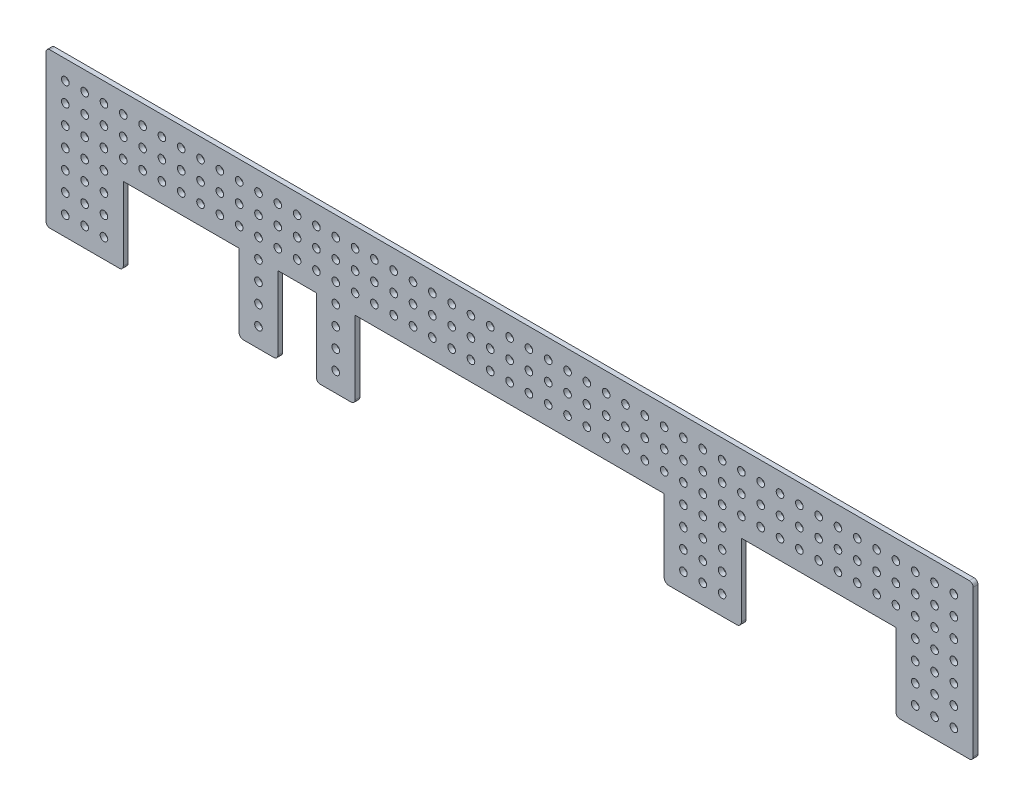
SolidWorks part; units mm, degrees
ref_plane "Front Plane" through (0, 0, 0) normal (0, 0, 1) x (1, 0, 0)
ref_plane "Top Plane" through (0, 0, 0) normal (0, 1, 0) x (1, 0, 0)
ref_plane "Right Plane" through (0, 0, 0) normal (1, 0, 0) x (0, 0, -1)
sketch "Sketch2" plane through (0, 0, 0) normal (0, 0, 1) x (1, 0, 0)
  line L1 (-478.1332, -46.4778) -> (126.3868, -46.4778)
  line L2 (-480.6732, -49.0178) -> (-480.6732, -97.2778)
  line L3 (-480.6732, -97.2778) -> (128.9268, -97.2778)
  line L4 (128.9268, -49.0178) -> (128.9268, -97.2778)
  line L5 (-480.6732, -97.2778) -> (-429.8732, -97.2778)
  line L6 (-480.6732, -97.2778) -> (-480.6732, -145.5378)
  line L7 (-478.1332, -148.0778) -> (-432.4132, -148.0778)
  line L8 (-429.8732, -97.2778) -> (-429.8732, -145.5378)
  line L9 (78.1268, -97.2778) -> (128.9268, -97.2778)
  line L10 (78.1268, -97.2778) -> (78.1268, -145.5378)
  line L11 (80.6668, -148.0778) -> (126.3868, -148.0778)
  line L12 (128.9268, -97.2778) -> (128.9268, -145.5378)
  arc A0 (78.1268, -145.5378) -> (80.6668, -148.0778) centre (80.6668, -145.5378) ccw
  arc A1 (126.3868, -148.0778) -> (128.9268, -145.5378) centre (126.3868, -145.5378) ccw
  arc A2 (126.3868, -46.4778) -> (128.9268, -49.0178) centre (126.3868, -49.0178) cw
  arc A3 (-432.4132, -148.0778) -> (-429.8732, -145.5378) centre (-432.4132, -145.5378) ccw
  arc A4 (-480.6732, -145.5378) -> (-478.1332, -148.0778) centre (-478.1332, -145.5378) ccw
  arc A5 (-478.1332, -46.4778) -> (-480.6732, -49.0178) centre (-478.1332, -49.0178) ccw
  point P16 (78.1268, -148.0778)
  point P19 (128.9268, -148.0778)
  point P22 (128.9268, -46.4778)
  point P25 (-429.8732, -148.0778)
  point P28 (-480.6732, -148.0778)
  dimension "D7" = 2.54
  dimension "D1" = 50.8
  dimension "D2" = 609.6
  dimension "D3" = 50.8
  dimension "D4" = 50.8
  dimension "3" = 50.8
  dimension "D6" = 50.8
extrude "Boss-Extrude1" add sketch "Sketch2" along normal blind 3.175 contours L4 L1 L2 L3 | L8 L3 L6 L7 | L12 L3 L10 L11 region at (-175.8732, -71.88, 0) region at (-455.2732, -122.6511, 0) region at (103.5268, -122.6511, 0)
sketch "Sketch3" plane through (0, 0, 3.175) normal (0, 0, 1) x (1, 0, 0)
  line L0 (-478.1332, -46.4778) -> (126.3868, -46.4778) construction
  line L1 (-480.6732, -49.0178) -> (-480.6732, -145.5378) construction
  line L2 (-478.1332, -148.0778) -> (-432.4132, -148.0778) construction
  line L3 (80.6668, -148.0778) -> (126.3868, -148.0778) construction
  line L4 (78.1268, -97.2778) -> (78.1268, -145.5378) construction
  circle A0 centre (-467.9732, -59.1778) radius 2.505
  circle A1 centre (-455.2732, -59.1778) radius 2.505
  circle A2 centre (-442.5732, -59.1778) radius 2.505
  circle A3 centre (-429.8732, -59.1778) radius 2.505
  circle A4 centre (-417.1732, -59.1778) radius 2.505
  circle A5 centre (-404.4732, -59.1778) radius 2.505
  circle A6 centre (-391.7732, -59.1778) radius 2.505
  circle A7 centre (-379.0732, -59.1778) radius 2.505
  circle A8 centre (-366.3732, -59.1778) radius 2.505
  circle A9 centre (-353.6732, -59.1778) radius 2.505
  circle A10 centre (-340.9732, -59.1778) radius 2.505
  circle A11 centre (-328.2732, -59.1778) radius 2.505
  circle A12 centre (-315.5732, -59.1778) radius 2.505
  circle A13 centre (-302.8732, -59.1778) radius 2.505
  circle A14 centre (-290.1732, -59.1778) radius 2.505
  circle A15 centre (-277.4732, -59.1778) radius 2.505
  circle A16 centre (-264.7732, -59.1778) radius 2.505
  circle A17 centre (-252.0732, -59.1778) radius 2.505
  circle A18 centre (-239.3732, -59.1778) radius 2.505
  circle A19 centre (-226.6732, -59.1778) radius 2.505
  circle A20 centre (-213.9732, -59.1778) radius 2.505
  circle A21 centre (-201.2732, -59.1778) radius 2.505
  circle A22 centre (-188.5732, -59.1778) radius 2.505
  circle A23 centre (-175.8732, -59.1778) radius 2.505
  circle A24 centre (-163.1732, -59.1778) radius 2.505
  circle A25 centre (-150.4732, -59.1778) radius 2.505
  circle A26 centre (-137.7732, -59.1778) radius 2.505
  circle A27 centre (-125.0732, -59.1778) radius 2.505
  circle A28 centre (-112.3732, -59.1778) radius 2.505
  circle A29 centre (-99.6732, -59.1778) radius 2.505
  circle A30 centre (-86.9732, -59.1778) radius 2.505
  circle A31 centre (-74.2732, -59.1778) radius 2.505
  circle A32 centre (-61.5732, -59.1778) radius 2.505
  circle A33 centre (-48.8732, -59.1778) radius 2.505
  circle A34 centre (-36.1732, -59.1778) radius 2.505
  circle A35 centre (-23.4732, -59.1778) radius 2.505
  circle A36 centre (-10.7732, -59.1778) radius 2.505
  circle A37 centre (1.9268, -59.1778) radius 2.505
  circle A38 centre (14.6268, -59.1778) radius 2.505
  circle A39 centre (27.3268, -59.1778) radius 2.505
  circle A40 centre (40.0268, -59.1778) radius 2.505
  circle A41 centre (52.7268, -59.1778) radius 2.505
  circle A42 centre (65.4268, -59.1778) radius 2.505
  circle A43 centre (78.1268, -59.1778) radius 2.505
  circle A44 centre (90.8268, -59.1778) radius 2.505
  circle A45 centre (103.5268, -59.1778) radius 2.505
  circle A46 centre (116.2268, -59.1778) radius 2.505
  circle A47 centre (-455.2732, -71.8778) radius 2.505
  circle A48 centre (-442.5732, -71.8778) radius 2.505
  circle A49 centre (-429.8732, -71.8778) radius 2.505
  circle A50 centre (-417.1732, -71.8778) radius 2.505
  circle A51 centre (-404.4732, -71.8778) radius 2.505
  circle A52 centre (-391.7732, -71.8778) radius 2.505
  circle A53 centre (-379.0732, -71.8778) radius 2.505
  circle A54 centre (-366.3732, -71.8778) radius 2.505
  circle A55 centre (-353.6732, -71.8778) radius 2.505
  circle A56 centre (-340.9732, -71.8778) radius 2.505
  circle A57 centre (-328.2732, -71.8778) radius 2.505
  circle A58 centre (-315.5732, -71.8778) radius 2.505
  circle A59 centre (-302.8732, -71.8778) radius 2.505
  circle A60 centre (-290.1732, -71.8778) radius 2.505
  circle A61 centre (-277.4732, -71.8778) radius 2.505
  circle A62 centre (-264.7732, -71.8778) radius 2.505
  circle A63 centre (-252.0732, -71.8778) radius 2.505
  circle A64 centre (-239.3732, -71.8778) radius 2.505
  circle A65 centre (-226.6732, -71.8778) radius 2.505
  circle A66 centre (-213.9732, -71.8778) radius 2.505
  circle A67 centre (-201.2732, -71.8778) radius 2.505
  circle A68 centre (-188.5732, -71.8778) radius 2.505
  circle A69 centre (-175.8732, -71.8778) radius 2.505
  circle A70 centre (-163.1732, -71.8778) radius 2.505
  circle A71 centre (-150.4732, -71.8778) radius 2.505
  circle A72 centre (-137.7732, -71.8778) radius 2.505
  circle A73 centre (-125.0732, -71.8778) radius 2.505
  circle A74 centre (-112.3732, -71.8778) radius 2.505
  circle A75 centre (-99.6732, -71.8778) radius 2.505
  circle A76 centre (-86.9732, -71.8778) radius 2.505
  circle A77 centre (-74.2732, -71.8778) radius 2.505
  circle A78 centre (-61.5732, -71.8778) radius 2.505
  circle A79 centre (-48.8732, -71.8778) radius 2.505
  circle A80 centre (-36.1732, -71.8778) radius 2.505
  circle A81 centre (-23.4732, -71.8778) radius 2.505
  circle A82 centre (-10.7732, -71.8778) radius 2.505
  circle A83 centre (1.9268, -71.8778) radius 2.505
  circle A84 centre (14.6268, -71.8778) radius 2.505
  circle A85 centre (27.3268, -71.8778) radius 2.505
  circle A86 centre (40.0268, -71.8778) radius 2.505
  circle A87 centre (52.7268, -71.8778) radius 2.505
  circle A88 centre (65.4268, -71.8778) radius 2.505
  circle A89 centre (78.1268, -71.8778) radius 2.505
  circle A90 centre (90.8268, -71.8778) radius 2.505
  circle A91 centre (103.5268, -71.8778) radius 2.505
  circle A92 centre (116.2268, -71.8778) radius 2.505
  circle A93 centre (-455.2732, -84.5778) radius 2.505
  circle A94 centre (-442.5732, -84.5778) radius 2.505
  circle A95 centre (-429.8732, -84.5778) radius 2.505
  circle A96 centre (-417.1732, -84.5778) radius 2.505
  circle A97 centre (-404.4732, -84.5778) radius 2.505
  circle A98 centre (-391.7732, -84.5778) radius 2.505
  circle A99 centre (-379.0732, -84.5778) radius 2.505
  circle A100 centre (-366.3732, -84.5778) radius 2.505
  circle A101 centre (-353.6732, -84.5778) radius 2.505
  circle A102 centre (-340.9732, -84.5778) radius 2.505
  circle A103 centre (-328.2732, -84.5778) radius 2.505
  circle A104 centre (-315.5732, -84.5778) radius 2.505
  circle A105 centre (-302.8732, -84.5778) radius 2.505
  circle A106 centre (-290.1732, -84.5778) radius 2.505
  circle A107 centre (-277.4732, -84.5778) radius 2.505
  circle A108 centre (-264.7732, -84.5778) radius 2.505
  circle A109 centre (-252.0732, -84.5778) radius 2.505
  circle A110 centre (-239.3732, -84.5778) radius 2.505
  circle A111 centre (-226.6732, -84.5778) radius 2.505
  circle A112 centre (-213.9732, -84.5778) radius 2.505
  circle A113 centre (-201.2732, -84.5778) radius 2.505
  circle A114 centre (-188.5732, -84.5778) radius 2.505
  circle A115 centre (-175.8732, -84.5778) radius 2.505
  circle A116 centre (-163.1732, -84.5778) radius 2.505
  circle A117 centre (-150.4732, -84.5778) radius 2.505
  circle A118 centre (-137.7732, -84.5778) radius 2.505
  circle A119 centre (-125.0732, -84.5778) radius 2.505
  circle A120 centre (-112.3732, -84.5778) radius 2.505
  circle A121 centre (-99.6732, -84.5778) radius 2.505
  circle A122 centre (-86.9732, -84.5778) radius 2.505
  circle A123 centre (-74.2732, -84.5778) radius 2.505
  circle A124 centre (-61.5732, -84.5778) radius 2.505
  circle A125 centre (-48.8732, -84.5778) radius 2.505
  circle A126 centre (-36.1732, -84.5778) radius 2.505
  circle A127 centre (-23.4732, -84.5778) radius 2.505
  circle A128 centre (-10.7732, -84.5778) radius 2.505
  circle A129 centre (1.9268, -84.5778) radius 2.505
  circle A130 centre (14.6268, -84.5778) radius 2.505
  circle A131 centre (27.3268, -84.5778) radius 2.505
  circle A132 centre (40.0268, -84.5778) radius 2.505
  circle A133 centre (52.7268, -84.5778) radius 2.505
  circle A134 centre (65.4268, -84.5778) radius 2.505
  circle A135 centre (78.1268, -84.5778) radius 2.505
  circle A136 centre (90.8268, -84.5778) radius 2.505
  circle A137 centre (103.5268, -84.5778) radius 2.505
  circle A138 centre (116.2268, -84.5778) radius 2.505
  circle A139 centre (-467.9732, -71.8778) radius 2.505
  circle A140 centre (-467.9732, -84.5778) radius 2.505
  circle A141 centre (-467.9732, -135.3778) radius 2.505
  circle A142 centre (-455.2732, -135.3778) radius 2.505
  circle A143 centre (-442.5732, -135.3778) radius 2.505
  circle A144 centre (-455.2732, -122.6778) radius 2.505
  circle A145 centre (-442.5732, -122.6778) radius 2.505
  circle A146 centre (-455.2732, -109.9778) radius 2.505
  circle A147 centre (-442.5732, -109.9778) radius 2.505
  circle A148 centre (-455.2732, -97.2778) radius 2.505
  circle A149 centre (-442.5732, -97.2778) radius 2.505
  circle A150 centre (-455.2732, -84.5778) radius 2.505
  circle A151 centre (-442.5732, -84.5778) radius 2.505
  circle A152 centre (-455.2732, -71.8778) radius 2.505
  circle A153 centre (-442.5732, -71.8778) radius 2.505
  circle A154 centre (-467.9732, -122.6778) radius 2.505
  circle A155 centre (-467.9732, -109.9778) radius 2.505
  circle A156 centre (-467.9732, -97.2778) radius 2.505
  circle A157 centre (-467.9732, -84.5778) radius 2.505
  circle A158 centre (-467.9732, -71.8778) radius 2.505
  circle A159 centre (90.8268, -135.3778) radius 2.505
  circle A160 centre (103.5268, -135.3778) radius 2.505
  circle A161 centre (116.2268, -135.3778) radius 2.505
  circle A162 centre (103.5268, -122.6778) radius 2.505
  circle A163 centre (116.2268, -122.6778) radius 2.505
  circle A164 centre (103.5268, -109.9778) radius 2.505
  circle A165 centre (116.2268, -109.9778) radius 2.505
  circle A166 centre (103.5268, -97.2778) radius 2.505
  circle A167 centre (116.2268, -97.2778) radius 2.505
  circle A168 centre (103.5268, -84.5778) radius 2.505
  circle A169 centre (116.2268, -84.5778) radius 2.505
  circle A170 centre (103.5268, -71.8778) radius 2.505
  circle A171 centre (116.2268, -71.8778) radius 2.505
  circle A172 centre (90.8268, -122.6778) radius 2.505
  circle A173 centre (90.8268, -109.9778) radius 2.505
  circle A174 centre (90.8268, -97.2778) radius 2.505
  circle A175 centre (90.8268, -84.5778) radius 2.505
  circle A176 centre (90.8268, -71.8778) radius 2.505
  dimension "5.01mm" = 5.01
  dimension "D6" = 5.01
  dimension "D11" = 5.01
  dimension "D2" = 12.7
  dimension "D3" = 12.7
  dimension "D7" = 12.7
  dimension "D8" = 12.7
  dimension "D12" = 12.7
  dimension "D13" = 12.7
  dimension "D4" = 47
  dimension "D5" = 3
  dimension "D9" = 3
  dimension "D10" = 6
  dimension "D14" = 3
  dimension "D15" = 6
extrude "Cut-Extrude1" cut sketch "Sketch3" against normal through all
sketch "Sketch4" plane through (0, 0, 3.175) normal (0, 0, 1) x (1, 0, 0)
  line L0 (-429.8732, -97.2778) -> (78.1268, -97.2778) construction
  line L1 (-353.6732, -97.2778) -> (-328.2732, -97.2778)
  line L2 (-353.6732, -97.2778) -> (-353.6732, -145.5378)
  line L3 (-351.1332, -148.0778) -> (-330.8132, -148.0778)
  line L4 (-328.2732, -97.2778) -> (-328.2732, -145.5378)
  line L5 (-302.8732, -97.2778) -> (-277.4732, -97.2778)
  line L6 (-302.8732, -97.2778) -> (-302.8732, -145.5378)
  line L7 (-300.3332, -148.0778) -> (-280.0132, -148.0778)
  line L8 (-277.4732, -97.2778) -> (-277.4732, -145.5378)
  line L9 (-429.8732, -97.2778) -> (-429.8732, -145.5378) construction
  arc A0 (-280.0132, -148.0778) -> (-277.4732, -145.5378) centre (-280.0132, -145.5378) ccw
  arc A1 (-302.8732, -145.5378) -> (-300.3332, -148.0778) centre (-300.3332, -145.5378) ccw
  arc A2 (-330.8132, -148.0778) -> (-328.2732, -145.5378) centre (-330.8132, -145.5378) ccw
  arc A3 (-353.6732, -145.5378) -> (-351.1332, -148.0778) centre (-351.1332, -145.5378) ccw
  point P14 (-277.4732, -148.0778)
  point P17 (-302.8732, -148.0778)
  point P20 (-328.2732, -148.0778)
  point P23 (-353.6732, -148.0778)
  dimension "D7" = 2.54
  dimension "D1" = 25.4
  dimension "D2" = 50.8
  dimension "D3" = 76.2
  dimension "D4" = 25.4
  dimension "D5" = 50.8
  dimension "D6" = 25.4
extrude "Boss-Extrude2" add sketch "Sketch4" against normal up to surface (3.175 mm away) up to face at (-33.6682, -71.8778, 0)
sketch "Sketch5" plane through (0, 0, 3.175) normal (0, 0, 1) x (1, 0, 0)
  line L0 (-277.4732, -145.5378) -> (-277.4732, -97.2778) construction
  line L1 (-300.3332, -148.0778) -> (-280.0132, -148.0778) construction
  line L4 (-351.1332, -148.0778) -> (-330.8132, -148.0778) construction
  line L5 (-353.6732, -97.2778) -> (-353.6732, -145.5378) construction
  circle A1 centre (-290.1732, -135.3778) radius 2.5
  circle A2 centre (-340.9732, -135.3778) radius 2.5
  circle A3 centre (-340.9732, -122.6778) radius 2.5
  circle A4 centre (-290.1732, -122.6778) radius 2.5
  circle A5 centre (-340.9732, -109.9778) radius 2.5
  circle A6 centre (-290.1732, -109.9778) radius 2.5
  circle A7 centre (-340.9732, -97.2778) radius 2.5
  circle A8 centre (-290.1732, -97.2778) radius 2.5
  dimension "D1" = 5
  dimension "D6" = 12.7
  dimension "D4" = 5
  dimension "D2" = 12.7
  dimension "D3" = 12.7
  dimension "D5" = 12.7
extrude "Cut-Extrude2" cut sketch "Sketch5" against normal through all
sketch "Sketch6" plane through (0, 0, 3.175) normal (0, 0, 1) x (1, 0, 0)
  line L0 (-277.4732, -97.2778) -> (78.1268, -97.2778) construction
  line L1 (-23.4732, -97.2778) -> (-74.2732, -97.2778)
  line L2 (-23.4732, -97.2778) -> (-23.4732, -144.9028)
  line L3 (-26.6482, -148.0778) -> (-71.0982, -148.0778)
  line L4 (-74.2732, -97.2778) -> (-74.2732, -144.9028)
  line L5 (78.1268, -97.2778) -> (78.1268, -145.5378) construction
  arc A0 (-23.4732, -144.9028) -> (-26.6482, -148.0778) centre (-26.6482, -144.9028) cw
  arc A1 (-71.0982, -148.0778) -> (-74.2732, -144.9028) centre (-71.0982, -144.9028) cw
  point P10 (-23.4732, -148.0778)
  dimension "D4" = 3.175
  dimension "D1" = 50.8
  dimension "D2" = 50.8
  dimension "D3" = 101.6
extrude "Boss-Extrude3" add sketch "Sketch6" against normal up to surface (3.175 mm away) up to face at (-338.4732, -109.9778, 0)
sketch "Sketch7" plane through (0, 0, 3.175) normal (0, 0, 1) x (1, 0, 0)
  line L0 (-74.2732, -97.2778) -> (-74.2732, -144.9028) construction
  line L1 (-71.0982, -148.0778) -> (-26.6482, -148.0778) construction
  circle A0 centre (-61.5732, -135.3778) radius 2.505
  circle A1 centre (-48.8732, -135.3778) radius 2.505
  circle A2 centre (-36.1732, -135.3778) radius 2.505
  circle A3 centre (-48.8732, -122.6778) radius 2.505
  circle A4 centre (-36.1732, -122.6778) radius 2.505
  circle A5 centre (-48.8732, -109.9778) radius 2.505
  circle A6 centre (-36.1732, -109.9778) radius 2.505
  circle A7 centre (-48.8732, -97.2778) radius 2.505
  circle A8 centre (-36.1732, -97.2778) radius 2.505
  circle A9 centre (-61.5732, -122.6778) radius 2.505
  circle A10 centre (-61.5732, -109.9778) radius 2.505
  circle A11 centre (-61.5732, -97.2778) radius 2.505
  dimension "D1" = 5.01
  dimension "D2" = 12.7
  dimension "D3" = 12.7
  dimension "D4" = 3
  dimension "D5" = 4
extrude "Cut-Extrude3" cut sketch "Sketch7" against normal through all
